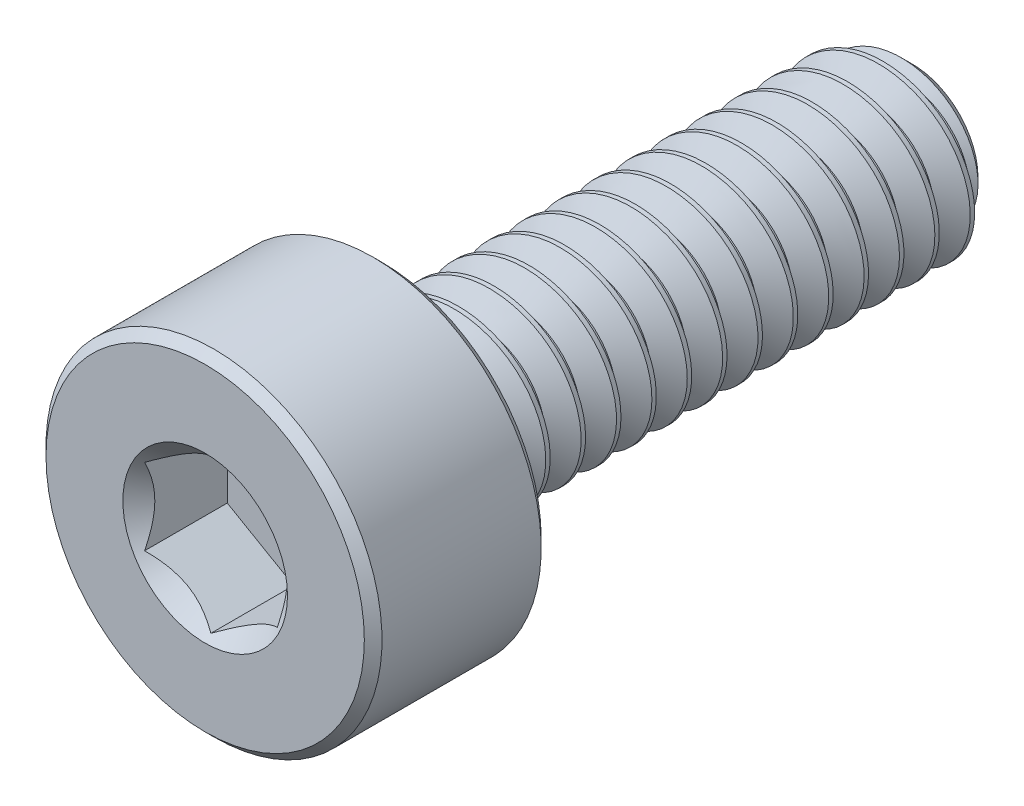
SolidWorks part; units mm, degrees
material "Plain Carbon Steel"
ref_plane "Front Plane" through (0, 0, 0) normal (0, 0, 1) x (1, 0, 0)
ref_plane "Top Plane" through (0, 0, 0) normal (0, 1, 0) x (1, 0, 0)
ref_plane "Right Plane" through (0, 0, 0) normal (1, 0, 0) x (0, 0, -1)
sketch "Sketch1" plane through (0, 0, 0) normal (1, 0, 0) x (0, 0, -1)
  line L0 (-4, 0) -> (4, 0) construction
  line L1 (4, 0) -> (4, 0.7402) construction
  line L2 (4, 0.7402) -> (3.7402, 1) construction
  line L3 (3.7402, 1) -> (3.7, 1) construction
  line L4 (3.7, 1) -> (-2, 1) construction
  line L5 (-2, 1) -> (-2, 1.9) construction
  line L6 (-2, 1.9) -> (-4, 1.9) construction
  line L7 (-4, 1.9) -> (-4, 0) construction
  line L8 (4, 0.7402) -> (4, 1) construction
  line L9 (3.975, 1.0433) -> (4.175, 0.6969) construction
  line L10 (4.175, 0.6969) -> (4.375, 1.0433) construction
  line L11 (4.375, 1.0433) -> (3.975, 1.0433) construction
  line L12 (4.175, 1.0433) -> (4.175, 1) construction
  line L13 (4.175, 0.6969) -> (4.175, 0.7402) construction
  line L14 (4.15, 0.7402) -> (4.2, 0.7402) construction
  line L15 (4, 1) -> (4.35, 1) construction
  line L16 (3.9875, 1.0217) -> (4.3625, 1.0217) construction
  line L17 (4, 0) -> (4, -1) construction
  line L18 (-2.1, 1.9) -> (-2, 1.8) construction
  line L19 (-3.9, 1.9) -> (-4, 1.8) construction
  line L20 (-2, 1) -> (-2, 0) construction
  line L21 (-2, 0.5) -> (0, 0.5) construction
  line L22 (0, 0.5) -> (2, 0.5) construction
  line L23 (2, 0.5) -> (4, 0.5) construction
  line L24 (0, 0.5) -> (0, 1) construction
  line L25 (0, 1) -> (0, 1.9) construction
  line L26 (2, 0.5) -> (2, 1.9) construction
  point P0 (-4, 0.75)
  point P3 (3, 1)
  point P4 (0, 0)
  point P18 (2, 1)
  point P22 (4.175, 0.7402)
  point P24 (3.7, 1)
  point P25 (4.175, 1)
  point P28 (4.175, 1.0217)
  point P29 (3, -1)
  point P30 (0, 1)
  point P31 (-3, 1.9)
  point P37 (-2.35, 1.9)
  point P38 (-3.85, 1.9)
  point P45 (0, 0.5)
  point P46 (2, 0.5)
  dimension "D2" = 0.05
  dimension "D7" = 0.1
  dimension "D8" = 0.1
  dimension "D9" = 0.1
  dimension "D10" = 0.05
  dimension "D11" = 0.25
  dimension "Drive Size" = 1.5
  dimension "Head Diameter" = 3.8
  dimension "Head Height" = 2
  dimension "Thread Pitch" = 0.4
  dimension "Thread Dia" = 2
  dimension "Length" = 6
  dimension "D12" = 0.3
  dimension "D4" = 1
  dimension "D3" = 45
sketch "Sketch2" plane through (0, 0, 0) normal (1, 0, 0) x (0, 0, -1)
  line L0 (-4, 0) -> (-4, 1.8)
  line L1 (-3.9, 1.9) -> (-2.1, 1.9)
  line L2 (-2, 1.8) -> (-2, 1.1)
  line L4 (3.7402, 1) -> (4, 0.7402)
  line L5 (4, 0.7402) -> (4, 0)
  line L6 (-2, 1.9) -> (-4, 1.9) construction
  line L7 (4, 0) -> (-4, 0)
  line L8 (-3.9, 1.9) -> (-4, 1.8) construction
  line L10 (-3.9, 1.9) -> (-4, 1.8)
  line L14 (-2.1, 1.9) -> (-2, 1.8) construction
  line L16 (-2.1, 1.9) -> (-2, 1.8)
  line L17 (-2, 1) -> (-2, 1.9) construction
  line L19 (-1.9, 1) -> (3.7402, 1)
  line L20 (3.7, 1) -> (-2, 1) construction
  arc A1 (-2, 1.1) -> (-1.9, 1) centre (-1.9, 1.1) ccw
  dimension "D3" = 0.1
revolve "Revolve1" add sketch "Sketch2" angle 360 about L7
sketch "Sketch3" plane through (0, 0, 4) normal (0, 0, 1) x (1, 0, 0)
  line L1 (0.75, -0.433) -> (0.75, 0.433)
  line L2 (0.75, 0.433) -> (0, 0.866)
  line L3 (0, 0.866) -> (-0.75, 0.433)
  line L4 (-0.75, 0.433) -> (-0.75, -0.433)
  line L5 (-0.75, -0.433) -> (0, -0.866)
  line L6 (0, -0.866) -> (0.75, -0.433)
  circle A0 centre (0, 0) radius 0.75 construction
  circle A1 centre (0, 0) radius 1.9 construction
  circle A2 centre (0, 0) radius 1.9 construction
  circle A3 centre (0, 0) radius 0.866 construction
  point P13 (0, 0)
  dimension "D1" = 1.7321
extrude "Cut-Extrude1" cut sketch "Sketch3" against normal offset from surface (1 mm away) 1 up to face at (0, 1.8, 2)
sketch "Sketch4" plane through (0, 0, 4) normal (0, 0, 1) x (1, 0, 0)
  circle A0 centre (0, 0) radius 0.931
  dimension "D1" = 1.862
extrude "Cut-Extrude2" cut sketch "Sketch4" against normal up to vertex (1 mm away) draft 45 up to point (0, 1.9, 3)
sketch "Sketch11" plane through (0, 0, 0) normal (1, 0, 0) x (0, 0, -1)
  line L0 (-4, 0) -> (4, 0) construction
  line L1 (-4, 0) -> (4, 0) construction
  line L2 (-0.875, 0) -> (-0.875, 1) construction
  line L3 (3.7, 1) -> (-2, 1) construction
  line L4 (2.875, 0) -> (2.875, 1) construction
  line L6 (4, 0.7402) -> (4, 1) construction
  point P2 (-0.875, 0)
  point P3 (2.875, 0)
  dimension "D1" = 1.125
  dimension "D2" = 1.125
sketch "Sketch6" plane through (0, 0, -4) normal (0, 0, -1) x (-1, 0, 0)
  circle A0 centre (0, 0) radius 1
curve "Helix/Spiral1" pitch 0.4 height 6.4 radius 1 centre (0, 0, -4) axis (0, 0, 1) start towards (0, 1, 0)
sketch "Sketch10" plane through (0, 0, 0) normal (1, 0, 0) x (0, 0, -1)
  line L0 (-1.9, -1.9) -> (-1.9, 1.9)
  line L5 (-4, 0) -> (4, 0) construction
  line L6 (-1.9, 1) -> (-1.9, -1) construction
  point P3 (-1.9, 0)
split "Split1" trim tools "Sketch10" bodies to split 106 resulting bodies 114 115
sketch "Sketch7" plane through (0, 0, 0) normal (1, 0, 0) x (0, 0, -1)
  line L0 (3.9875, 1.0217) -> (4.3625, 1.0217)
  line L1 (4.3625, 1.0217) -> (4.2, 0.7402)
  line L2 (4.2, 0.7402) -> (4.15, 0.7402)
  line L3 (4.15, 0.7402) -> (3.9875, 1.0217)
sweep "Cut-Sweep1" cut profiles "Sketch7" path "Helix/Spiral1" align with end faces yes
sketch "Sketch8" plane through (0, 0, 0) normal (1, 0, 0) x (0, 0, -1)
  line L0 (-2, 0) -> (-2, 1)
  line L1 (-1.9, -1) -> (-1.9, 1) construction
  line L2 (-2, 1) -> (-1.9, 1)
  line L4 (-1.9, 1) -> (-1.3226, 0)
  line L5 (-1.3226, 0) -> (-2, 0)
  line L6 (3.7, 1) -> (-2, 1) construction
  line L7 (-4, 0) -> (4, 0) construction
  dimension "D1" = 60
revolve "Revolve2" add sketch "Sketch8" angle 360 about L5
equation "\"D2@Sketch1\" = \"Thread Pitch@Sketch1\" / 8"
equation "\"D4@Helix/Spiral1\" = \"Thread Pitch@Sketch1\""
equation "\"D7@Sketch1\" = \"Head Height@Sketch1\" * .05"
equation "\"D8@Sketch1\"=\"D7@Sketch1\""
equation "\"D9@Sketch1\"=\"D7@Sketch1\""
equation "\"D10@Sketch1\"=\"D7@Sketch1\"/2"
equation "\"D11@Sketch1\"=\"D10@Sketch1\"*5"
equation "\"D4@Sketch1\"=\"Thread Pitch@Sketch1\"*2.5"
equation "\"D12@Sketch1\"=\"Thread Pitch@Sketch1\"*.75"
equation "\"D3@Helix/Spiral1\"=\"Length@Sketch1\"+\"Thread Pitch@Sketch1\""
equation "\"D3@Sketch2\"=\"Thread Dia@Sketch1\"*0.05"
equation "\"D1@Sketch11\"=\"Length@Sketch1\"*0.1875"
equation "\"D2@Sketch11\"=\"D1@Sketch11\""
equation "\"D1@Sketch4\"=\"D1@Sketch3\"*1.075"
